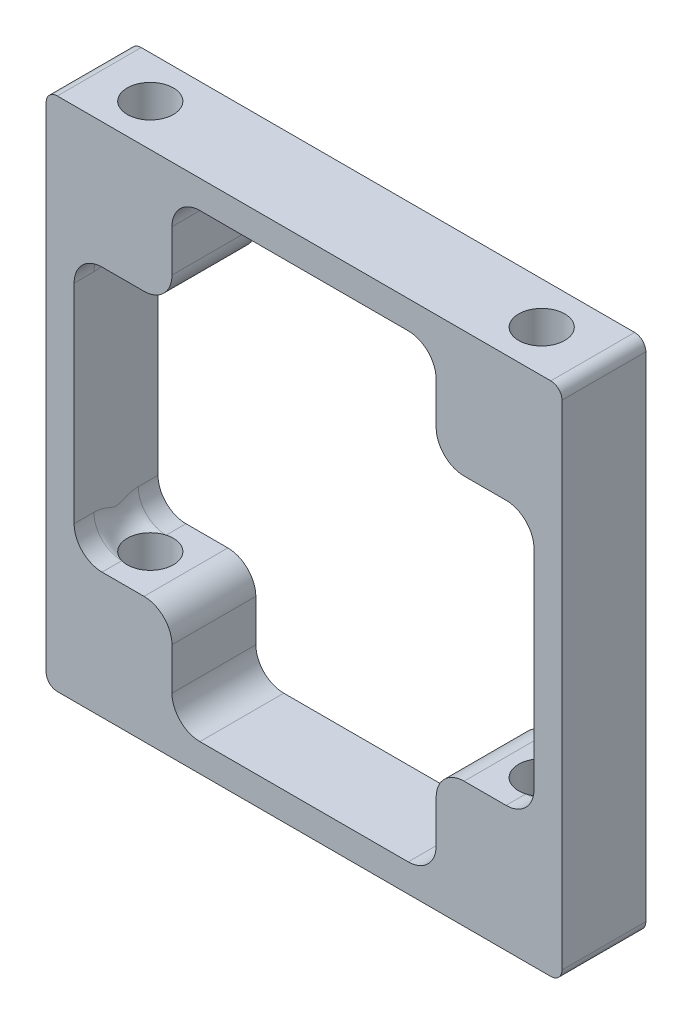
SolidWorks part; units mm, degrees
material "1060 合金"
ref_plane "前视基准面" through (0, 0, 0) normal (0, 0, 1) x (1, 0, 0)
ref_plane "上视基准面" through (0, 0, 0) normal (0, 1, 0) x (1, 0, 0)
ref_plane "右视基准面" through (0, 0, 0) normal (1, 0, 0) x (0, 0, -1)
other "Configuration Table"
sketch "草图1" plane through (0, 0, 0) normal (0, 0, 1) x (1, 0, 0)
  line L1 (-18.45, -18.45) -> (18.45, -18.45)
  line L2 (-18.45, -18.45) -> (-18.45, 18.45)
  line L3 (-18.45, 18.45) -> (18.45, 18.45)
  line L4 (18.45, -18.45) -> (18.45, 18.45)
  line L5 (-18.45, -18.45) -> (18.45, 18.45) construction
  line L6 (-18.45, 18.45) -> (18.45, -18.45) construction
  point P0 (0, 0)
  dimension "D1" = 36.9
extrude "凸台-拉伸1" add sketch "草图1" along normal mid plane 6
sketch "草图2" plane through (0, 18.45, 0) normal (0, 1, 0) x (1, 0, 0)
  line L0 (-14, 0) -> (14, 0) construction
  circle A0 centre (-14, 0) radius 1
  circle A1 centre (14, 0) radius 1
  point P4 (0, 0)
  dimension "D2" = 2
  dimension "D1" = 28
extrude "切除-拉伸1" cut sketch "草图2" against normal blind 10
fillet "圆角2" radius 0.8 4 edges at (18.45, -18.45, 0) (-18.45, -18.45, 0) (-18.45, 18.45, 0) (18.45, 18.45, 0)
hole_wizard "M4 螺纹孔1" positions "草图5" profile "草图6" tap size "M4" standard "GB"
sketch "草图5" plane through (0, 18.45, 0) normal (0, 1, 0) x (1, 0, 0)
  point P0 (-14, 0)
  point P3 (14, 0)
sketch "草图6" plane through (-14, 18.45, 0) normal (1, 0, 0) x (0, 0, 1)
  line L0 (0, 0) -> (0, 10.9914)
  line L1 (0, 10.9914) -> (1.65, 10)
  line L2 (1.65, 10) -> (1.65, 0)
  line L5 (1.65, 0) -> (0, 0)
  line L10 (0, 10.9914) -> (-1.65, 10) construction
  line L11 (0, -6.35) -> (0, 107.95) construction
  dimension "螺纹孔钻头直径" = 3.3
  dimension "螺纹孔钻头深度" = 10
  dimension "导头角度" = 118
cosmetic thread "孔螺蚊线1" parameters "D1"=8, "D2"=4
cosmetic thread "孔螺蚊线2" parameters "D1"=8, "D2"=4
mirror "镜向1" about plane through (0, 0, 0) normal (0, 1, 0) of "M4 螺纹孔1"
sketch "草图7" plane through (0, 0, 3) normal (0, 0, 1) x (1, 0, 0)
  line L0 (-9.45, 16.45) -> (9.45, 16.45)
  line L1 (0, 0) -> (50000, 0) construction
  line L2 (-9.45, 16.45) -> (-9.45, 9.45)
  line L3 (-9.45, 9.45) -> (-16.45, 9.45)
  line L4 (-16.45, 9.45) -> (-16.45, -9.45)
  line L5 (9.45, 16.45) -> (9.45, 9.45)
  line L6 (9.45, 9.45) -> (16.45, 9.45)
  line L7 (16.45, 9.45) -> (16.45, -9.45)
  line L8 (0, 0) -> (0, -50000) construction
  line L9 (-18.45, 17.65) -> (-18.45, -17.65) construction
  line L10 (17.65, 18.45) -> (-17.65, 18.45) construction
  line L12 (-16.45, 9.45) -> (-16.45, 0)
  line L13 (-9.45, 9.45) -> (-16.45, 9.45)
  line L14 (-9.45, 16.45) -> (-9.45, 9.45)
  line L15 (16.45, 9.45) -> (16.45, 0)
  line L16 (9.45, 9.45) -> (16.45, 9.45)
  line L17 (9.45, 16.45) -> (9.45, 9.45)
  line L18 (-9.45, 16.45) -> (-9.45, 9.45)
  line L19 (-9.45, 9.45) -> (-16.45, 9.45)
  line L20 (-16.45, 9.45) -> (-16.45, 0)
  line L21 (9.45, 16.45) -> (9.45, 9.45)
  line L22 (9.45, 9.45) -> (16.45, 9.45)
  line L23 (16.45, 9.45) -> (16.45, 0)
  line L24 (-16.45, 9.45) -> (-16.45, 0)
  line L25 (-9.45, 9.45) -> (-16.45, 9.45)
  line L26 (-9.45, 16.45) -> (-9.45, 9.45)
  line L27 (16.45, 9.45) -> (16.45, 0)
  line L28 (9.45, 9.45) -> (16.45, 9.45)
  line L29 (9.45, 16.45) -> (9.45, 9.45)
  line L30 (9.45, -9.45) -> (16.45, -9.45)
  line L31 (9.45, -16.45) -> (9.45, -9.45)
  line L32 (-9.45, -16.45) -> (9.45, -16.45)
  line L33 (-9.45, -16.45) -> (-9.45, -9.45)
  line L34 (-9.45, -9.45) -> (-16.45, -9.45)
  dimension "D1" = 2
  dimension "D2" = 9
  dimension "D3" = 9
  dimension "D4" = 2
extrude "切除-拉伸2" cut sketch "草图7" against normal mid plane 20 contours L34 L33 L32 L31 L30 L7 L6 L5 L0 L2 L3 L4 region at (0, 0, 3)
fillet "圆角3" radius 2 12 edges at (-16.45, 9.45, 0) (-9.45, 16.45, 0) (9.45, 16.45, 0) (9.45, 9.45, 0) (16.45, 9.45, 0) (16.45, -9.45, 0) (9.45, -9.45, 0) (9.45, -16.45, 0) (-9.45, -16.45, 0) (-9.45, -9.45, 0) (-16.45, -9.45, 0) (-9.45, 9.45, 0)
